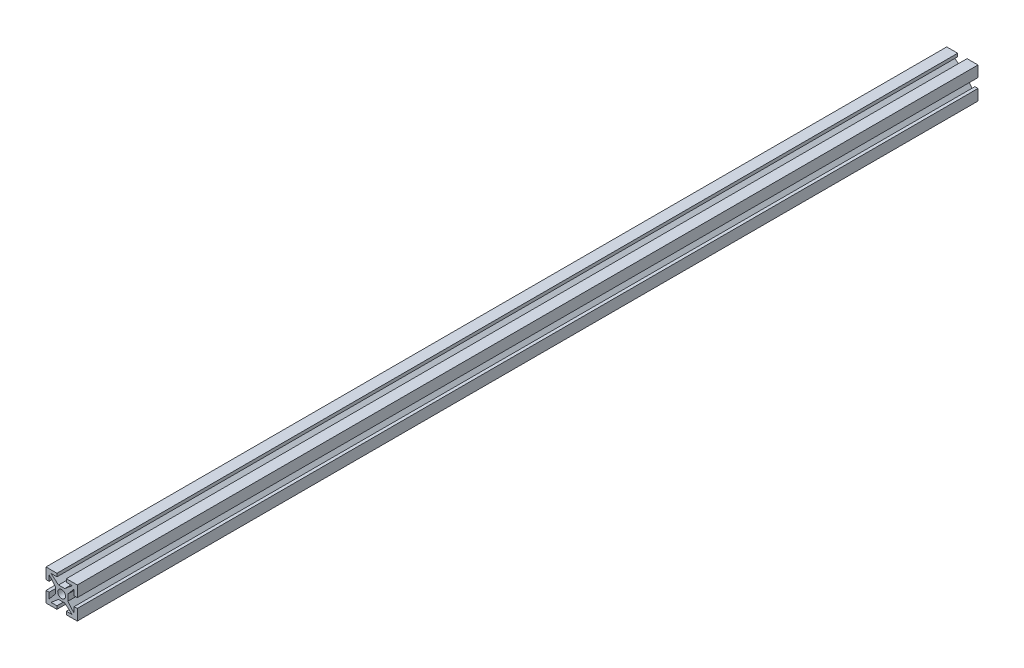
SolidWorks part; units mm, degrees
ref_plane "Front Plane" through (0, 0, 0) normal (0, 0, 1) x (1, 0, 0)
ref_plane "Top Plane" through (0, 0, 0) normal (0, 1, 0) x (1, 0, 0)
ref_plane "Right Plane" through (0, 0, 0) normal (1, 0, 0) x (0, 0, -1)
sketch "Esquisse2" plane through (0, 0, 0) normal (0, 0, 1) x (1, 0, 0)
  line L0 (-1, -2) -> (1, -2)
  line L1 (1, -2) -> (3.3835, -4)
  line L2 (3.3835, -4) -> (1.5, -4)
  line L3 (1.5, -4) -> (1.5, -5)
  line L4 (1.5, -5) -> (5, -5)
  line L5 (-1, -2) -> (-3.3835, -4)
  line L6 (-3.3835, -4) -> (-1.5, -4)
  line L7 (-1.5, -4) -> (-1.5, -5)
  line L8 (-1.5, -5) -> (-5, -5)
  line L9 (-5, -5) -> (-5, -1.5)
  line L10 (-5, -1.5) -> (-4, -1.5)
  line L11 (-4, -1.5) -> (-4, -3.3835)
  line L12 (-4, -3.3835) -> (-2, -1)
  line L13 (-2, -1) -> (-2, 1)
  line L14 (-2, 1) -> (-4, 3.3835)
  line L15 (-4, 3.3835) -> (-4, 1.5)
  line L16 (-4, 1.5) -> (-5, 1.5)
  line L17 (-5, 1.5) -> (-5, 5)
  line L18 (-5, 5) -> (-1.5, 5)
  line L19 (-1.5, 5) -> (-1.5, 4)
  line L20 (-1.5, 4) -> (-3.3835, 4)
  line L21 (-3.3835, 4) -> (-1, 2)
  line L22 (-1, 2) -> (1, 2)
  line L23 (1, 2) -> (3.3835, 4)
  line L24 (3.3835, 4) -> (1.5, 4)
  line L25 (1.5, 4) -> (1.5, 5)
  line L26 (1.5, 5) -> (5, 5)
  line L27 (5, 5) -> (5, 1.5)
  line L28 (5, 1.5) -> (4, 1.5)
  line L29 (4, 1.5) -> (4, 3.3835)
  line L30 (4, 3.3835) -> (2, 1)
  line L31 (2, -1) -> (2, 1)
  line L32 (2, -1) -> (4, -3.3835)
  line L33 (4, -3.3835) -> (4, -1.5)
  line L34 (4, -1.5) -> (5, -1.5)
  line L35 (5, -1.5) -> (5, -5)
  circle A0 centre (0, 0) radius 1.25
  point P4 (0, -2)
  point P34 (0, 2)
  point P40 (2, 0)
  dimension "D4" = 2.5
  dimension "D1" = 2
  dimension "D2" = 3.5
  dimension "D3" = 1
  dimension "D5" = 10
  dimension "D6" = 10
  dimension "D7" = 140
  dimension "D8" = 4
  dimension "D9" = 4
  dimension "D10" = 3.5
  dimension "D11" = 3
extrude "Main Extrusion" add sketch "Esquisse2" along normal blind 288
